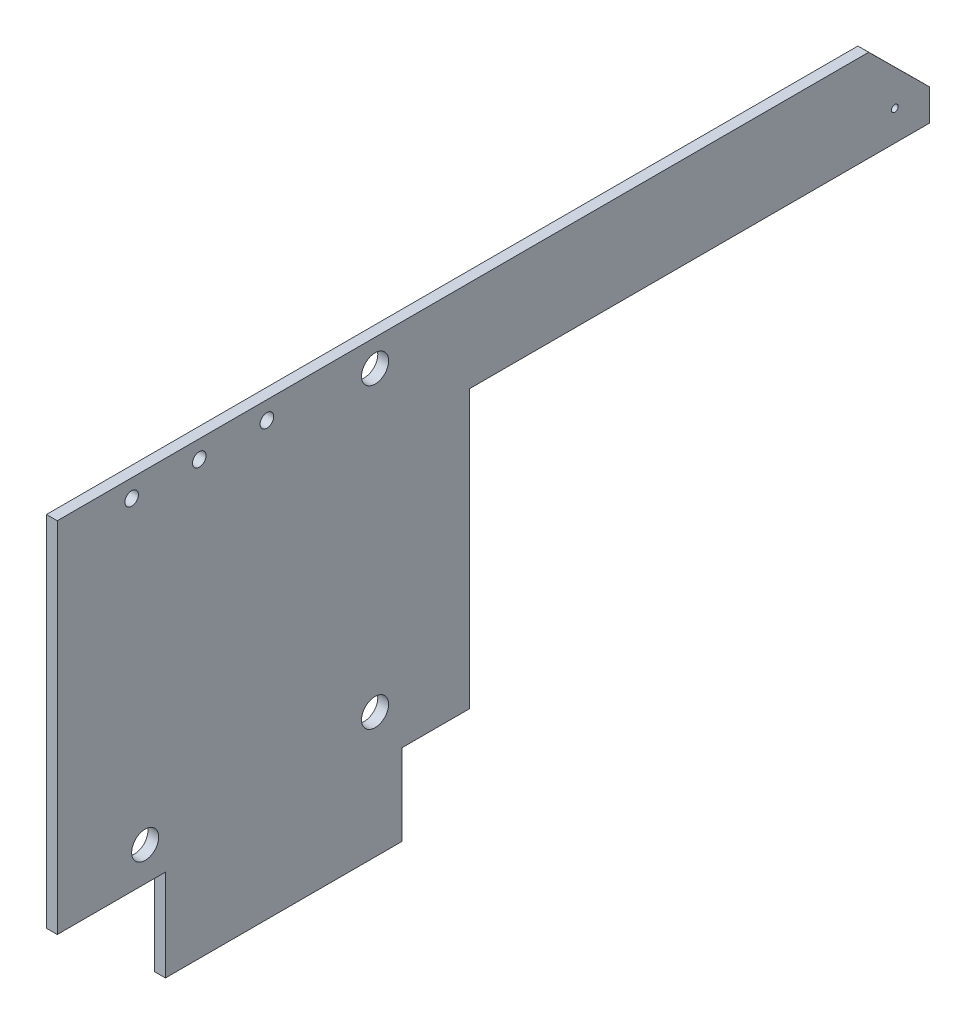
SolidWorks part; units mm, degrees
ref_plane "Front Plane" through (0, 0, 0) normal (0, 0, 1) x (1, 0, 0)
ref_plane "Top Plane" through (0, 0, 0) normal (0, 1, 0) x (1, 0, 0)
ref_plane "Right Plane" through (0, 0, 0) normal (1, 0, 0) x (0, 0, -1)
sketch "Sketch1" plane through (0, 0, 0) normal (1, 0, 0) x (0, 0, -1)
  line L0 (3, 11) -> (3, 64)
  line L1 (3, 64) -> (123, 64)
  line L2 (123, 64) -> (132, 55.0634)
  line L3 (132, 55.0634) -> (132, 50.4234)
  line L4 (132, 50.4234) -> (64, 50.4234)
  line L5 (64, 50.4234) -> (64, 9.4361)
  line L6 (64, 9.4361) -> (54, 9.4361)
  line L7 (54, 9.4361) -> (54, -2.5639)
  line L8 (54, -2.5639) -> (19, -2.5639)
  line L9 (19, -2.5639) -> (19, 11)
  line L10 (19, 11) -> (3, 11)
  line L11 (125.6318, 53.6442) -> (129.503, 57.5428) construction
  line L12 (129.503, 57.5428) -> (114.3538, 42.2861) construction
  circle A0 centre (16, 16) radius 2
  circle A1 centre (50, 16) radius 2
  circle A2 centre (50, 60) radius 2
  circle A3 centre (14, 61.35) radius 1
  circle A4 centre (24, 61.35) radius 1
  circle A5 centre (34, 61.35) radius 1
  circle A6 centre (126.8618, 54.8829) radius 0.5
  circle A7 centre (14, 61.35) radius 0.5 construction
  circle A8 centre (24, 61.35) radius 0.5 construction
  circle A9 centre (34, 61.35) radius 0.5 construction
  circle A12 centre (50, 60) radius 2 construction
  circle A13 centre (50, 16) radius 2 construction
  circle A14 centre (16, 16) radius 2 construction
  circle A15 centre (126.8618, 54.8829) radius 0.5 construction
  point P28 (4.95, 8.3843)
  dimension "D1" = 2
  dimension "D2" = 120
  dimension "D3" = 16
  dimension "D4" = 10
  dimension "D5" = 35
  dimension "D6" = 68
  dimension "D7" = 53
  dimension "D8" = 13.5639
  dimension "D9" = 40.9874
  dimension "D10" = 12
  dimension "D11" = 11
  dimension "D12" = 3
extrude "Boss-Extrude1" add sketch "Sketch1" along normal blind 1.6
